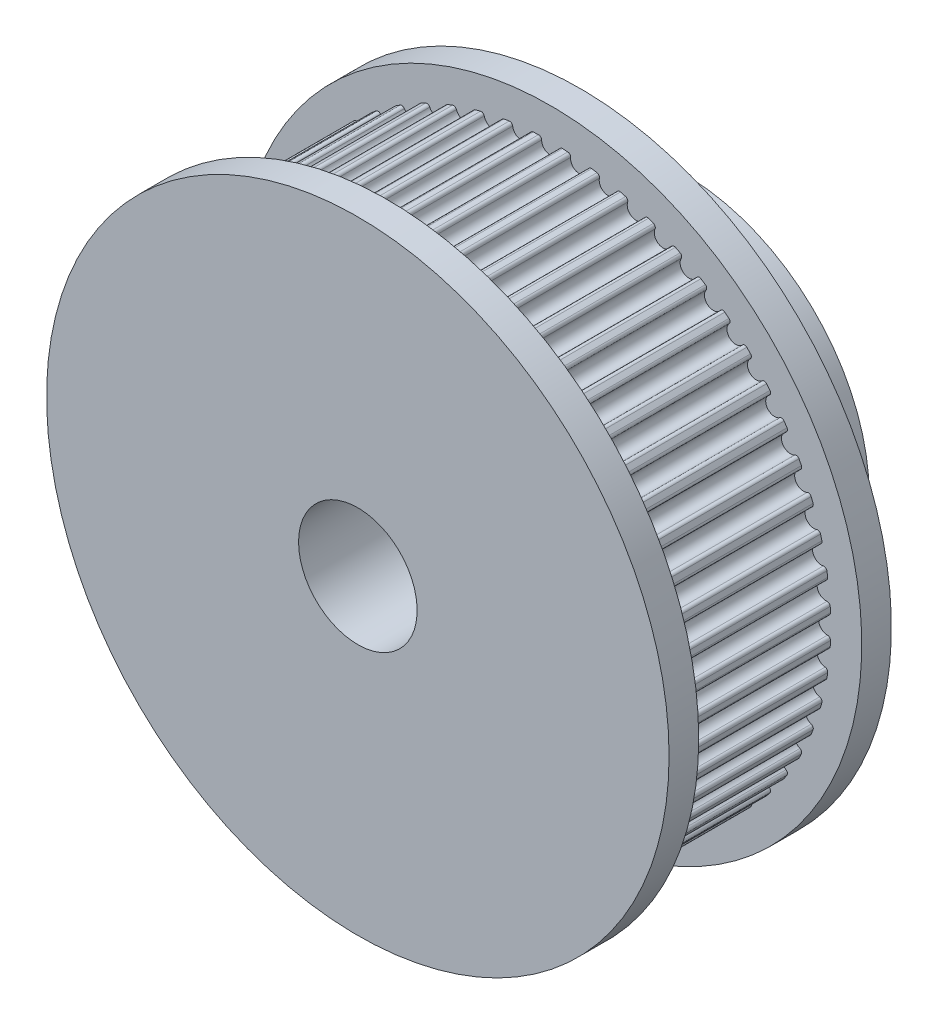
SolidWorks part; units mm, degrees
ref_plane "Front Plane" through (0, 0, 0) normal (0, 0, 1) x (1, 0, 0)
ref_plane "Top Plane" through (0, 0, 0) normal (0, 1, 0) x (1, 0, 0)
ref_plane "Right Plane" through (0, 0, 0) normal (1, 0, 0) x (0, 0, -1)
ref_axis "Axis1" through (0, 0, 55) along (0, 0, -1)
sketch "SketchRevolveGearBelt02" plane through (0, 0, 0) normal (1, 0, 0) x (0, 0, -1)
  line L0 (0, 0) -> (1, 0) construction
  line L1 (5.5, 0) -> (5.5, 18.9081)
  line L2 (5.5, 18.9081) -> (-5.5, 18.9081)
  line L3 (-5.5, 18.9081) -> (-5.5, 0)
  line L4 (-5.5, 0) -> (5.5, 0)
  dimension "GearBeltSide1" = 5.5
  dimension "GearBeltOutsideDiameter" = 18.9081
  dimension "GearBeltSide2" = 5.5
revolve "GearBelt02" add sketch "SketchRevolveGearBelt02" angle 360 about L0
sketch "SketchToothGearBelt02" plane through (0, 0, 0) normal (0, 0, 1) x (1, 0, 0)
  line L0 (-0.8105, 18.8907) -> (0, 21.4481)
  line L1 (0, 21.4481) -> (0.8105, 18.8907)
  arc A0 (0.8105, 18.8907) -> (0.6, 18.6891) centre (0.8018, 18.6891) ccw
  arc A1 (0.6, 18.6891) -> (-0.6, 18.6891) centre (0, 18.6891) cw
  arc A2 (-0.6, 18.6891) -> (-0.8105, 18.8907) centre (-0.8018, 18.6891) ccw
  dimension "GearBeltToothR1" = 0.4036
  dimension "GearBeltToothR2" = 1.2
  dimension "GearBeltToothCapX1" = 0.8105
  dimension "GearBeltToothCapY1" = 2.5574
  dimension "GearBeltToothCapX2" = 0.8105
  dimension "GearBeltToothCapY2" = 2.5574
extrude "ToothExtrudeCutGearBelt02" cut sketch "SketchToothGearBelt02" against normal blind 5.6 and the other way blind 5.6
pattern_circular "PatternGearBelt02" count 60 every 6 about axis through (0, 0, 55) along (0, 0, -1) of "ToothExtrudeCutGearBelt02"
sketch "Sketch5" plane through (0, 0, 5.5) normal (0, 0, 1) x (1, 0, 0)
  circle A0 centre (0, 0) radius 21
extrude "Boss-Extrude1" add sketch "Sketch5" along normal blind 2
sketch "Sketch6" plane through (0, 0, -5.5) normal (0, 0, -1) x (-1, 0, 0)
  circle A0 centre (0, 0) radius 21
extrude "Boss-Extrude2" add sketch "Sketch6" along normal blind 2
sketch "Sketch7" plane through (0, 0, -7.5) normal (0, 0, -1) x (-1, 0, 0)
  circle A0 centre (0, 0) radius 12.5
extrude "Boss-Extrude3" add sketch "Sketch7" along normal blind 7
sketch "Sketch8" plane through (0, 0, -14.5) normal (0, 0, -1) x (-1, 0, 0)
  circle A0 centre (0, 0) radius 4
extrude "Cut-Extrude2" cut sketch "Sketch8" against normal through all
